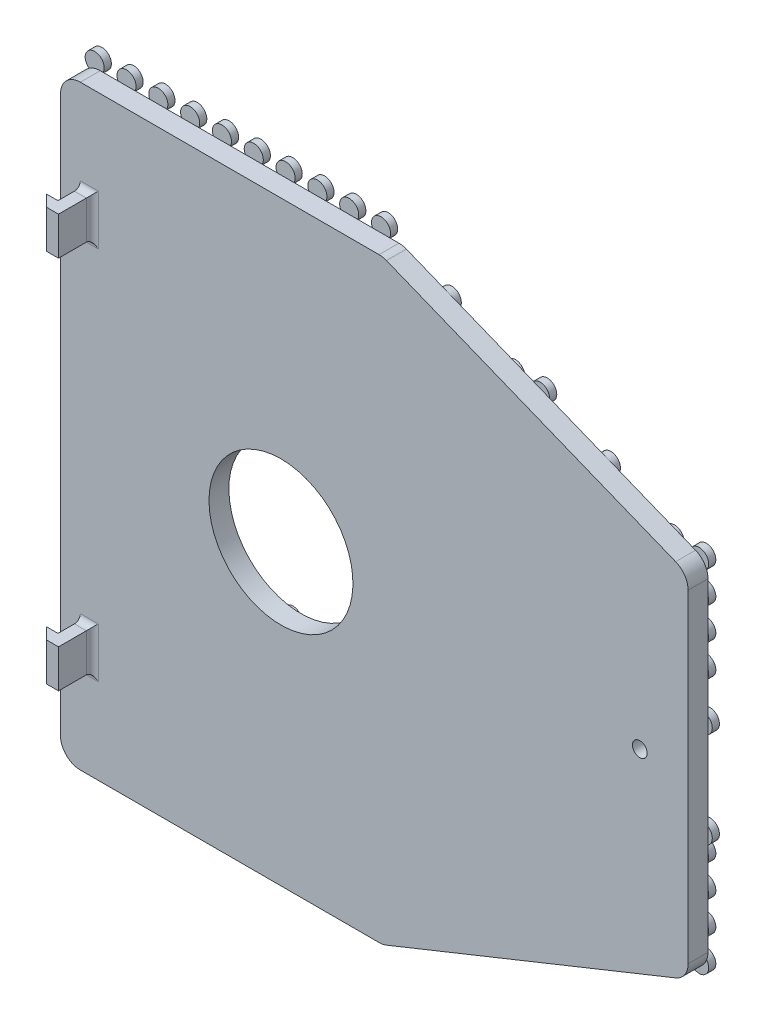
SolidWorks part; units mm, degrees
ref_plane "Plan de face" through (0, 0, 0) normal (0, 0, 1) x (1, 0, 0)
ref_plane "Plan de dessus" through (0, 0, 0) normal (0, 1, 0) x (1, 0, 0)
ref_plane "Plan de droite" through (0, 0, 0) normal (1, 0, 0) x (0, 0, -1)
sketch "Esquisse1" plane through (0, 0, -49) normal (0, 0, -1) x (-1, 0, 0)
  line L1 (88.4422, -5.1503) -> (88.4422, 144.6564)
  line L3 (8.331, -5.1503) -> (83.4432, -5.1503) construction
  line L4 (7.3641, -5.1503) -> (88.4422, -5.1503)
  line L5 (-66.2517, 24.4313) -> (6.467, -4.7898) construction
  line L6 (88.4422, -0.1513) -> (88.4422, 139.6574) construction
  line L7 (83.4432, 144.6564) -> (8.331, 144.6564) construction
  line L8 (6.467, 144.2959) -> (-66.2517, 115.0748) construction
  line L9 (-69.3867, 110.4363) -> (-69.3867, 29.0698) construction
  line L11 (7.3641, 144.6564) -> (-69.3867, 113.815)
  line L14 (-69.3867, 25.6911) -> (7.3641, -5.1503)
  line L15 (-69.3867, 113.815) -> (-69.3867, 25.6911)
  line L17 (88.4422, 144.6564) -> (7.3641, 144.6564)
  circle A0 centre (32.9994, 69.753) radius 18.1
  circle A1 centre (32.9994, 69.753) radius 18 construction
  dimension "D1" = 0.1
extrude "Boss.-Extru.1" add sketch "Esquisse1" along normal blind 5
sketch "Esquisse4" plane through (0, 0, -54) normal (0, 0, -1) x (-1, 0, 0)
  circle A0 centre (-57.2408, 69.753) radius 1.85
  arc A1 (-61.4834, 71.253) -> (-52.9981, 68.253) centre (-57.2408, 69.753) ccw construction
  dimension "D1" = 3.7
extrude "Enlèv. mat.-Extru.1" cut sketch "Esquisse4" against normal up to surface (5 mm away) up to face at (-8.8065, 69.753, -49)
sketch "Esquisse5" plane through (0, 0, -54) normal (0, 0, -1) x (-1, 0, 0)
  circle A0 centre (-57.2408, 69.753) radius 5
  dimension "D1" = 10
extrude "Enlèv. mat.-Extru.2" cut sketch "Esquisse5" against normal blind 2
sketch "Esquisse15" plane through (0, 0, -54) normal (0, 0, -1) x (-1, 0, 0)
  line L0 (84.8422, 144.6564) -> (84.8422, -36.2839) construction
  line L1 (68.8422, 145.753) -> (68.8422, 144.6564) construction
  line L2 (-69.3867, 25.6911) -> (7.3641, -5.1503) construction
  line L3 (84.8422, 145.753) -> (84.8422, 137.753) construction
  line L4 (68.8422, -6.247) -> (68.8422, -5.1503) construction
  line L5 (84.8422, 145.753) -> (76.8422, 145.753) construction
  line L6 (84.8422, 9.753) -> (84.8422, 1.753) construction
  line L7 (76.8422, 1.753) -> (76.8422, -6.247) construction
  line L8 (12.8422, 137.753) -> (4.8422, 137.753) construction
  line L9 (-3.1578, 129.753) -> (-11.1578, 129.753) construction
  line L10 (-27.1578, 121.753) -> (-35.1578, 121.753) construction
  line L11 (-43.1578, 113.753) -> (-51.1578, 113.753) construction
  line L12 (88.4422, -5.1503) -> (88.4422, 144.6564) construction
  line L13 (88.4422, 144.6564) -> (7.3641, 144.6564) construction
  line L14 (7.3641, -5.1503) -> (88.4422, -5.1503) construction
  circle A0 centre (84.8422, 145.753) radius 2.4
  circle A1 centre (84.8422, 137.753) radius 2.4
  circle A2 centre (84.8422, 129.753) radius 2.4
  circle A3 centre (84.8422, 121.753) radius 2.4
  circle A4 centre (84.8422, 113.753) radius 2.4
  circle A5 centre (84.8422, 105.753) radius 2.4
  circle A6 centre (84.8422, 97.753) radius 2.4
  circle A7 centre (84.8422, 89.753) radius 2.4
  circle A8 centre (84.8422, 81.753) radius 2.4
  circle A9 centre (84.8422, 73.753) radius 2.4
  circle A10 centre (84.8422, 65.753) radius 2.4
  circle A11 centre (84.8422, 57.753) radius 2.4
  circle A12 centre (84.8422, 49.753) radius 2.4
  circle A13 centre (84.8422, 41.753) radius 2.4
  circle A14 centre (84.8422, 33.753) radius 2.4
  circle A15 centre (84.8422, 25.753) radius 2.4
  circle A16 centre (84.8422, 17.753) radius 2.4
  circle A17 centre (84.8422, 9.753) radius 2.4
  circle A18 centre (76.8422, 145.753) radius 2.4
  circle A19 centre (76.8422, 137.753) radius 2.4
  circle A20 centre (76.8422, 129.753) radius 2.4
  circle A21 centre (76.8422, 121.753) radius 2.4
  circle A22 centre (76.8422, 113.753) radius 2.4
  circle A23 centre (76.8422, 105.753) radius 2.4
  circle A24 centre (76.8422, 97.753) radius 2.4
  circle A25 centre (76.8422, 89.753) radius 2.4
  circle A26 centre (76.8422, 81.753) radius 2.4
  circle A27 centre (76.8422, 73.753) radius 2.4
  circle A28 centre (76.8422, 9.753) radius 2.4
  circle A29 centre (76.8422, 17.753) radius 2.4
  circle A30 centre (76.8422, 25.753) radius 2.4
  circle A31 centre (76.8422, 33.753) radius 2.4
  circle A32 centre (76.8422, 41.753) radius 2.4
  circle A33 centre (76.8422, 49.753) radius 2.4
  circle A34 centre (76.8422, 57.753) radius 2.4
  circle A35 centre (76.8422, 65.753) radius 2.4
  circle A36 centre (68.8422, 145.753) radius 2.4
  circle A37 centre (68.8422, 137.753) radius 2.4
  circle A38 centre (68.8422, 129.753) radius 2.4
  circle A39 centre (68.8422, 121.753) radius 2.4
  circle A40 centre (68.8422, 113.753) radius 2.4
  circle A41 centre (68.8422, 105.753) radius 2.4
  circle A42 centre (68.8422, 97.753) radius 2.4
  circle A43 centre (68.8422, 89.753) radius 2.4
  circle A44 centre (68.8422, 81.753) radius 2.4
  circle A45 centre (68.8422, 73.753) radius 2.4
  circle A46 centre (68.8422, 9.753) radius 2.4
  circle A47 centre (68.8422, 17.753) radius 2.4
  circle A48 centre (68.8422, 25.753) radius 2.4
  circle A49 centre (68.8422, 33.753) radius 2.4
  circle A50 centre (68.8422, 41.753) radius 2.4
  circle A51 centre (68.8422, 49.753) radius 2.4
  circle A52 centre (68.8422, 57.753) radius 2.4
  circle A53 centre (68.8422, 65.753) radius 2.4
  circle A54 centre (60.8422, 145.753) radius 2.4
  circle A55 centre (60.8422, 137.753) radius 2.4
  circle A56 centre (60.8422, 129.753) radius 2.4
  circle A57 centre (60.8422, 121.753) radius 2.4
  circle A58 centre (60.8422, 113.753) radius 2.4
  circle A59 centre (60.8422, 105.753) radius 2.4
  circle A60 centre (60.8422, 97.753) radius 2.4
  circle A61 centre (60.8422, 89.753) radius 2.4
  circle A62 centre (60.8422, 81.753) radius 2.4
  circle A63 centre (60.8422, 73.753) radius 2.4
  circle A64 centre (60.8422, 9.753) radius 2.4
  circle A65 centre (60.8422, 17.753) radius 2.4
  circle A66 centre (60.8422, 25.753) radius 2.4
  circle A67 centre (60.8422, 33.753) radius 2.4
  circle A68 centre (60.8422, 41.753) radius 2.4
  circle A69 centre (60.8422, 49.753) radius 2.4
  circle A70 centre (60.8422, 57.753) radius 2.4
  circle A71 centre (60.8422, 65.753) radius 2.4
  circle A72 centre (52.8422, 145.753) radius 2.4
  circle A73 centre (52.8422, 137.753) radius 2.4
  circle A74 centre (52.8422, 129.753) radius 2.4
  circle A75 centre (52.8422, 121.753) radius 2.4
  circle A76 centre (52.8422, 113.753) radius 2.4
  circle A77 centre (52.8422, 105.753) radius 2.4
  circle A78 centre (52.8422, 97.753) radius 2.4
  circle A79 centre (52.8422, 89.753) radius 2.4
  circle A80 centre (52.8422, 81.753) radius 2.4
  circle A81 centre (36.7833, 48.1034) radius 2.4
  circle A82 centre (52.8422, 9.753) radius 2.4
  circle A83 centre (52.8422, 17.753) radius 2.4
  circle A84 centre (52.8422, 25.753) radius 2.4
  circle A85 centre (52.8422, 33.753) radius 2.4
  circle A86 centre (52.8422, 41.753) radius 2.4
  circle A87 centre (52.8422, 49.753) radius 2.4
  circle A88 centre (52.8422, 57.753) radius 2.4
  circle A89 centre (28.7243, 46.4537) radius 2.4
  circle A90 centre (44.8422, 145.753) radius 2.4
  circle A91 centre (44.8422, 137.753) radius 2.4
  circle A92 centre (44.8422, 129.753) radius 2.4
  circle A93 centre (44.8422, 121.753) radius 2.4
  circle A94 centre (44.8422, 113.753) radius 2.4
  circle A95 centre (44.8422, 105.753) radius 2.4
  circle A96 centre (44.8422, 97.753) radius 2.4
  circle A97 centre (44.8422, 89.753) radius 2.4
  circle A100 centre (44.8422, 9.753) radius 2.4
  circle A101 centre (44.8422, 17.753) radius 2.4
  circle A102 centre (44.8422, 25.753) radius 2.4
  circle A103 centre (44.8422, 33.753) radius 2.4
  circle A104 centre (44.8422, 41.753) radius 2.4
  circle A105 centre (44.8422, 49.753) radius 2.4
  circle A108 centre (36.8422, 145.753) radius 2.4
  circle A109 centre (36.8422, 137.753) radius 2.4
  circle A110 centre (36.8422, 129.753) radius 2.4
  circle A111 centre (36.8422, 121.753) radius 2.4
  circle A112 centre (36.8422, 113.753) radius 2.4
  circle A113 centre (36.8422, 105.753) radius 2.4
  circle A114 centre (36.8422, 97.753) radius 2.4
  circle A115 centre (36.8422, 89.753) radius 2.4
  circle A118 centre (36.8422, 9.753) radius 2.4
  circle A119 centre (36.8422, 17.753) radius 2.4
  circle A120 centre (36.8422, 25.753) radius 2.4
  circle A121 centre (36.8422, 33.753) radius 2.4
  circle A122 centre (36.8422, 41.753) radius 2.4
  circle A126 centre (28.8422, 145.753) radius 2.4
  circle A127 centre (28.8422, 137.753) radius 2.4
  circle A128 centre (28.8422, 129.753) radius 2.4
  circle A129 centre (28.8422, 121.753) radius 2.4
  circle A130 centre (28.8422, 113.753) radius 2.4
  circle A131 centre (28.8422, 105.753) radius 2.4
  circle A132 centre (28.8422, 97.753) radius 2.4
  circle A133 centre (28.8422, 89.753) radius 2.4
  circle A136 centre (28.8422, 9.753) radius 2.4
  circle A137 centre (28.8422, 17.753) radius 2.4
  circle A138 centre (28.8422, 25.753) radius 2.4
  circle A139 centre (28.8422, 33.753) radius 2.4
  circle A140 centre (28.8422, 41.753) radius 2.4
  circle A144 centre (20.8422, 145.753) radius 2.4
  circle A145 centre (20.8422, 137.753) radius 2.4
  circle A146 centre (20.8422, 129.753) radius 2.4
  circle A147 centre (20.8422, 121.753) radius 2.4
  circle A148 centre (20.8422, 113.753) radius 2.4
  circle A149 centre (20.8422, 105.753) radius 2.4
  circle A150 centre (20.8422, 97.753) radius 2.4
  circle A151 centre (20.8422, 89.753) radius 2.4
  circle A154 centre (20.8422, 9.753) radius 2.4
  circle A155 centre (20.8422, 17.753) radius 2.4
  circle A156 centre (20.8422, 25.753) radius 2.4
  circle A157 centre (20.8422, 33.753) radius 2.4
  circle A158 centre (20.8422, 41.753) radius 2.4
  circle A159 centre (20.8422, 49.753) radius 2.4
  circle A162 centre (12.8422, 145.753) radius 2.4
  circle A163 centre (12.8422, 137.753) radius 2.4
  circle A164 centre (12.8422, 129.753) radius 2.4
  circle A165 centre (12.8422, 121.753) radius 2.4
  circle A166 centre (12.8422, 113.753) radius 2.4
  circle A167 centre (12.8422, 105.753) radius 2.4
  circle A168 centre (12.8422, 97.753) radius 2.4
  circle A169 centre (12.8422, 89.753) radius 2.4
  circle A170 centre (12.8422, 81.753) radius 2.4
  circle A171 centre (12.8422, 73.753) radius 2.4
  circle A172 centre (12.8422, 9.753) radius 2.4
  circle A173 centre (12.8422, 17.753) radius 2.4
  circle A174 centre (12.8422, 25.753) radius 2.4
  circle A175 centre (12.8422, 33.753) radius 2.4
  circle A176 centre (12.8422, 41.753) radius 2.4
  circle A177 centre (12.8422, 49.753) radius 2.4
  circle A178 centre (12.8422, 57.753) radius 2.4
  circle A179 centre (12.8422, 65.753) radius 2.4
  circle A180 centre (84.8422, 1.753) radius 2.4
  circle A181 centre (76.8422, 1.753) radius 2.4
  circle A182 centre (68.8422, 1.753) radius 2.4
  circle A183 centre (60.8422, 1.753) radius 2.4
  circle A184 centre (52.8422, 1.753) radius 2.4
  circle A185 centre (44.8422, 1.753) radius 2.4
  circle A186 centre (36.8422, 1.753) radius 2.4
  circle A187 centre (28.8422, 1.753) radius 2.4
  circle A188 centre (20.8422, 1.753) radius 2.4
  circle A189 centre (12.8422, 1.753) radius 2.4
  circle A190 centre (76.8422, -6.247) radius 2.4
  circle A191 centre (68.8422, -6.247) radius 2.4
  circle A192 centre (84.8422, -6.247) radius 2.4
  circle A193 centre (60.8422, -6.247) radius 2.4
  circle A194 centre (52.8422, -6.247) radius 2.4
  circle A195 centre (44.8422, -6.247) radius 2.4
  circle A196 centre (36.8422, -6.247) radius 2.4
  circle A197 centre (28.8422, -6.247) radius 2.4
  circle A198 centre (20.8422, -6.247) radius 2.4
  circle A199 centre (12.8422, -6.247) radius 2.4
  circle A200 centre (4.8422, 137.753) radius 2.4
  circle A201 centre (4.8422, 129.753) radius 2.4
  circle A202 centre (4.8422, 121.753) radius 2.4
  circle A203 centre (4.8422, 113.753) radius 2.4
  circle A204 centre (4.8422, 105.753) radius 2.4
  circle A205 centre (4.8422, 97.753) radius 2.4
  circle A206 centre (4.8422, 89.753) radius 2.4
  circle A207 centre (4.8422, 81.753) radius 2.4
  circle A208 centre (4.8422, 73.753) radius 2.4
  circle A209 centre (4.8422, 9.753) radius 2.4
  circle A210 centre (4.8422, 17.753) radius 2.4
  circle A211 centre (4.8422, 25.753) radius 2.4
  circle A212 centre (4.8422, 33.753) radius 2.4
  circle A213 centre (4.8422, 41.753) radius 2.4
  circle A214 centre (4.8422, 49.753) radius 2.4
  circle A215 centre (4.8422, 57.753) radius 2.4
  circle A216 centre (4.8422, 65.753) radius 2.4
  circle A217 centre (4.8422, 1.753) radius 2.4
  circle A218 centre (-3.1578, 137.753) radius 2.4
  circle A219 centre (-3.1578, 129.753) radius 2.4
  circle A220 centre (-3.1578, 121.753) radius 2.4
  circle A221 centre (-3.1578, 113.753) radius 2.4
  circle A222 centre (-3.1578, 105.753) radius 2.4
  circle A223 centre (-3.1578, 97.753) radius 2.4
  circle A224 centre (-3.1578, 89.753) radius 2.4
  circle A225 centre (-3.1578, 81.753) radius 2.4
  circle A226 centre (-3.1578, 73.753) radius 2.4
  circle A227 centre (-3.1578, 9.753) radius 2.4
  circle A228 centre (-3.1578, 17.753) radius 2.4
  circle A229 centre (-3.1578, 25.753) radius 2.4
  circle A230 centre (-3.1578, 33.753) radius 2.4
  circle A231 centre (-3.1578, 41.753) radius 2.4
  circle A232 centre (-3.1578, 49.753) radius 2.4
  circle A233 centre (-3.1578, 57.753) radius 2.4
  circle A234 centre (-3.1578, 65.753) radius 2.4
  circle A235 centre (-3.1578, 1.753) radius 2.4
  circle A236 centre (-11.1578, 129.753) radius 2.4
  circle A237 centre (-11.1578, 121.753) radius 2.4
  circle A238 centre (-11.1578, 113.753) radius 2.4
  circle A239 centre (-11.1578, 105.753) radius 2.4
  circle A240 centre (-11.1578, 97.753) radius 2.4
  circle A241 centre (-11.1578, 89.753) radius 2.4
  circle A242 centre (-11.1578, 81.753) radius 2.4
  circle A243 centre (-11.1578, 73.753) radius 2.4
  circle A244 centre (-11.1578, 9.753) radius 2.4
  circle A245 centre (-11.1578, 17.753) radius 2.4
  circle A246 centre (-11.1578, 25.753) radius 2.4
  circle A247 centre (-11.1578, 33.753) radius 2.4
  circle A248 centre (-11.1578, 41.753) radius 2.4
  circle A249 centre (-11.1578, 49.753) radius 2.4
  circle A250 centre (-11.1578, 57.753) radius 2.4
  circle A251 centre (-11.1578, 65.753) radius 2.4
  circle A252 centre (-19.1578, 129.753) radius 2.4
  circle A253 centre (-19.1578, 121.753) radius 2.4
  circle A254 centre (-19.1578, 113.753) radius 2.4
  circle A255 centre (-19.1578, 105.753) radius 2.4
  circle A256 centre (-19.1578, 97.753) radius 2.4
  circle A257 centre (-19.1578, 89.753) radius 2.4
  circle A258 centre (-19.1578, 81.753) radius 2.4
  circle A259 centre (-19.1578, 73.753) radius 2.4
  circle A260 centre (-19.1578, 9.753) radius 2.4
  circle A261 centre (-19.1578, 17.753) radius 2.4
  circle A262 centre (-19.1578, 25.753) radius 2.4
  circle A263 centre (-19.1578, 33.753) radius 2.4
  circle A264 centre (-19.1578, 41.753) radius 2.4
  circle A265 centre (-19.1578, 49.753) radius 2.4
  circle A266 centre (-19.1578, 57.753) radius 2.4
  circle A267 centre (-19.1578, 65.753) radius 2.4
  circle A268 centre (-27.1578, 129.753) radius 2.4
  circle A269 centre (-27.1578, 121.753) radius 2.4
  circle A270 centre (-27.1578, 113.753) radius 2.4
  circle A271 centre (-27.1578, 105.753) radius 2.4
  circle A272 centre (-27.1578, 97.753) radius 2.4
  circle A273 centre (-27.1578, 89.753) radius 2.4
  circle A274 centre (-27.1578, 81.753) radius 2.4
  circle A275 centre (-27.1578, 73.753) radius 2.4
  circle A276 centre (-27.1578, 9.753) radius 2.4
  circle A277 centre (-27.1578, 17.753) radius 2.4
  circle A278 centre (-27.1578, 25.753) radius 2.4
  circle A279 centre (-27.1578, 33.753) radius 2.4
  circle A280 centre (-27.1578, 41.753) radius 2.4
  circle A281 centre (-27.1578, 49.753) radius 2.4
  circle A282 centre (-27.1578, 57.753) radius 2.4
  circle A283 centre (-27.1578, 65.753) radius 2.4
  circle A284 centre (-35.1578, 121.753) radius 2.4
  circle A285 centre (-35.1578, 113.753) radius 2.4
  circle A286 centre (-35.1578, 105.753) radius 2.4
  circle A287 centre (-35.1578, 97.753) radius 2.4
  circle A288 centre (-35.1578, 89.753) radius 2.4
  circle A289 centre (-35.1578, 81.753) radius 2.4
  circle A290 centre (-35.1578, 73.753) radius 2.4
  circle A291 centre (-35.1578, 17.753) radius 2.4
  circle A292 centre (-35.1578, 25.753) radius 2.4
  circle A293 centre (-35.1578, 33.753) radius 2.4
  circle A294 centre (-35.1578, 41.753) radius 2.4
  circle A295 centre (-35.1578, 49.753) radius 2.4
  circle A296 centre (-35.1578, 57.753) radius 2.4
  circle A297 centre (-35.1578, 65.753) radius 2.4
  circle A298 centre (-43.1578, 121.753) radius 2.4
  circle A299 centre (-43.1578, 113.753) radius 2.4
  circle A300 centre (-43.1578, 105.753) radius 2.4
  circle A301 centre (-43.1578, 97.753) radius 2.4
  circle A302 centre (-43.1578, 89.753) radius 2.4
  circle A303 centre (-43.1578, 81.753) radius 2.4
  circle A304 centre (-43.1578, 73.753) radius 2.4
  circle A305 centre (-43.1578, 17.753) radius 2.4
  circle A306 centre (-43.1578, 25.753) radius 2.4
  circle A307 centre (-43.1578, 33.753) radius 2.4
  circle A308 centre (-43.1578, 41.753) radius 2.4
  circle A309 centre (-43.1578, 49.753) radius 2.4
  circle A310 centre (-43.1578, 57.753) radius 2.4
  circle A311 centre (-43.1578, 65.753) radius 2.4
  circle A312 centre (-51.1578, 113.753) radius 2.4
  circle A313 centre (-51.1578, 105.753) radius 2.4
  circle A314 centre (-51.1578, 97.753) radius 2.4
  circle A315 centre (-51.1578, 89.753) radius 2.4
  circle A316 centre (-52.0611, 78.453) radius 2.4
  circle A317 centre (-52.0611, 54.453) radius 2.4
  circle A318 centre (-51.1578, 25.753) radius 2.4
  circle A319 centre (-51.1578, 33.753) radius 2.4
  circle A320 centre (-51.1578, 41.753) radius 2.4
  circle A321 centre (-51.1578, 49.753) radius 2.4
  circle A322 centre (-68.0611, 78.453) radius 2.4
  circle A323 centre (-68.0611, 54.453) radius 2.4
  circle A324 centre (-59.1578, 113.753) radius 2.4
  circle A325 centre (-59.1578, 105.753) radius 2.4
  circle A326 centre (-59.1578, 97.753) radius 2.4
  circle A327 centre (-59.1578, 89.753) radius 2.4
  circle A330 centre (-59.1578, 25.753) radius 2.4
  circle A331 centre (-59.1578, 33.753) radius 2.4
  circle A332 centre (-59.1578, 41.753) radius 2.4
  circle A333 centre (-59.1578, 49.753) radius 2.4
  circle A336 centre (-67.1578, 113.753) radius 2.4
  circle A337 centre (-67.1578, 105.753) radius 2.4
  circle A338 centre (-67.1578, 97.753) radius 2.4
  circle A339 centre (-67.1578, 89.753) radius 2.4
  circle A342 centre (-67.1578, 25.753) radius 2.4
  circle A343 centre (-67.1578, 33.753) radius 2.4
  circle A344 centre (-67.1578, 41.753) radius 2.4
  circle A345 centre (-67.1578, 49.753) radius 2.4
  circle A348 centre (-59.1578, 73.753) radius 2.4 [skipped]
  circle A349 centre (-59.1578, 81.753) radius 2.4 [skipped]
  circle A350 centre (-51.1578, 73.753) radius 2.4 [skipped]
  circle A351 centre (-59.1578, 65.753) radius 2.4 [skipped]
  circle A352 centre (-67.1578, 73.753) radius 2.4 [skipped]
  circle A353 centre (-51.1578, 81.753) radius 2.4 [skipped]
  circle A354 centre (-67.1578, 81.753) radius 2.4 [skipped]
  circle A355 centre (-51.1578, 65.753) radius 2.4 [skipped]
  circle A356 centre (-67.1578, 65.753) radius 2.4 [skipped]
  circle A357 centre (-51.1578, 57.753) radius 2.4 [skipped]
  circle A358 centre (-59.1578, 57.753) radius 2.4 [skipped]
  circle A359 centre (-67.1578, 57.753) radius 2.4 [skipped]
  circle A360 centre (28.8422, 81.753) radius 2.4 [skipped]
  circle A361 centre (20.8422, 81.753) radius 2.4 [skipped]
  circle A362 centre (20.8422, 73.753) radius 2.4 [skipped]
  circle A363 centre (20.8422, 65.753) radius 2.4 [skipped]
  circle A364 centre (28.8422, 73.753) radius 2.4 [skipped]
  circle A365 centre (36.8422, 81.753) radius 2.4 [skipped]
  circle A366 centre (36.8422, 73.753) radius 2.4 [skipped]
  circle A367 centre (44.8422, 73.753) radius 2.4 [skipped]
  circle A368 centre (44.8422, 81.753) radius 2.4 [skipped]
  circle A369 centre (52.8422, 73.753) radius 2.4 [skipped]
  circle A370 centre (52.8422, 65.753) radius 2.4 [skipped]
  circle A371 centre (44.8422, 57.753) radius 2.4 [skipped]
  circle A372 centre (36.8422, 57.753) radius 2.4 [skipped]
  circle A373 centre (28.8422, 57.753) radius 2.4 [skipped]
  circle A374 centre (28.8422, 65.753) radius 2.4 [skipped]
  circle A375 centre (20.8422, 57.753) radius 2.4 [skipped]
  circle A376 centre (36.8422, 65.753) radius 2.4 [skipped]
  circle A377 centre (44.8422, 65.753) radius 2.4 [skipped]
  circle A378 centre (36.8422, 49.753) radius 2.4 [skipped]
  circle A379 centre (28.8422, 49.753) radius 2.4 [skipped]
  dimension "D1" = 4.8
  dimension "D5" = 3
  dimension "D3" = 8
  dimension "D4" = 3.6
  dimension "D7" = 8
  dimension "D9" = 8
  dimension "D11" = 8
  dimension "D13" = 8
  dimension "D15" = 8
  dimension "D17" = 8
  dimension "D19" = 8
  dimension "D22" = 16
  dimension "D2" = 18
  dimension "D6" = 10
  dimension "D8" = 2
  dimension "D10" = 2
  dimension "D12" = 3
  dimension "D14" = 4
  dimension "D16" = 3
  dimension "D18" = 4
  dimension "D20" = 2
  dimension "D21" = 2
extrude "Boss.-Extru.5" add sketch "Esquisse15" along normal blind 1.8
sketch "Esquisse17" plane through (0, 0, -49) normal (0, 0, 1) x (1, 0, 0)
  line L0 (-86.5389, 17.638) -> (-84.3418, 17.638) construction
  line L1 (-83.4422, 17.838) -> (-80.4422, 17.838)
  line L2 (-83.4422, 17.838) -> (-83.4422, 27.438)
  line L3 (-83.4422, 27.438) -> (-80.4422, 27.438)
  line L4 (-80.4422, 17.838) -> (-80.4422, 27.438)
  line L5 (-86.5389, 27.638) -> (-84.3418, 27.638) construction
  line L6 (-84.4422, 2.8489) -> (-84.4422, 136.6572) construction
  line L7 (-84.4422, 69.753) -> (69.3867, 69.753) construction
  line L8 (69.3867, 113.815) -> (69.3867, 25.6911) construction
  line L9 (-83.4422, 112.068) -> (-80.4422, 112.068)
  line L10 (-83.4422, 121.668) -> (-83.4422, 112.068)
  line L11 (-80.4422, 121.668) -> (-80.4422, 112.068)
  line L12 (-83.4422, 121.668) -> (-80.4422, 121.668)
  dimension "D1" = 3
  dimension "D2" = 0.2
  dimension "D3" = 0.2
  dimension "D4" = 1
extrude "Boss.-Extru.6" add sketch "Esquisse17" along normal offset from surface (8.5 mm away) 0.5
sketch "Esquisse18" plane through (0, 121.668, 0) normal (0, 1, 0) x (1, 0, 0)
  line L0 (-83.4422, 40.5) -> (-86.3143, 43.3722)
  line L1 (-86.3143, 43.3722) -> (-83.4422, 43.3722)
  line L2 (-83.4422, 40.5) -> (-83.4422, 49) construction
  line L3 (-83.4422, 43.3722) -> (-83.4422, 40.5)
extrude "Boss.-Extru.7" add sketch "Esquisse18" against normal up to surface (9.6 mm away) up to face at (-81.9422, 112.068, -44.75)
sketch "Esquisse19" plane through (0, 17.838, 0) normal (0, -1, 0) x (1, 0, 0)
  line L0 (-83.4422, -40.5) -> (-86.3143, -43.3722) construction
  line L1 (-86.3143, -43.3722) -> (-83.4422, -43.3722) construction
  line L2 (-83.4422, -40.5) -> (-86.3143, -43.3722)
  line L3 (-86.3143, -43.3722) -> (-83.4422, -43.3722)
  line L4 (-83.4422, -40.5) -> (-83.4422, -43.3722)
extrude "Boss.-Extru.8" add sketch "Esquisse19" against normal up to surface (9.6 mm away) up to face at (-81.9422, 27.438, -44.75)
fillet "Congé1" radius 5 6 edges at (-7.3641, -5.1503, -51.5) (69.3867, 25.6911, -51.5) (69.3867, 113.815, -51.5) (-7.3641, 144.6564, -51.5) (-88.4422, 144.6564, -51.5) (-88.4422, -5.1503, -51.5)
fillet "Congé2" radius 1.5 6 edges at (-80.4422, 22.638, -49) (-81.9422, 17.838, -49) (-81.9422, 27.438, -49) (-81.9422, 112.068, -49) (-80.4422, 116.868, -49) (-81.9422, 121.668, -49)
